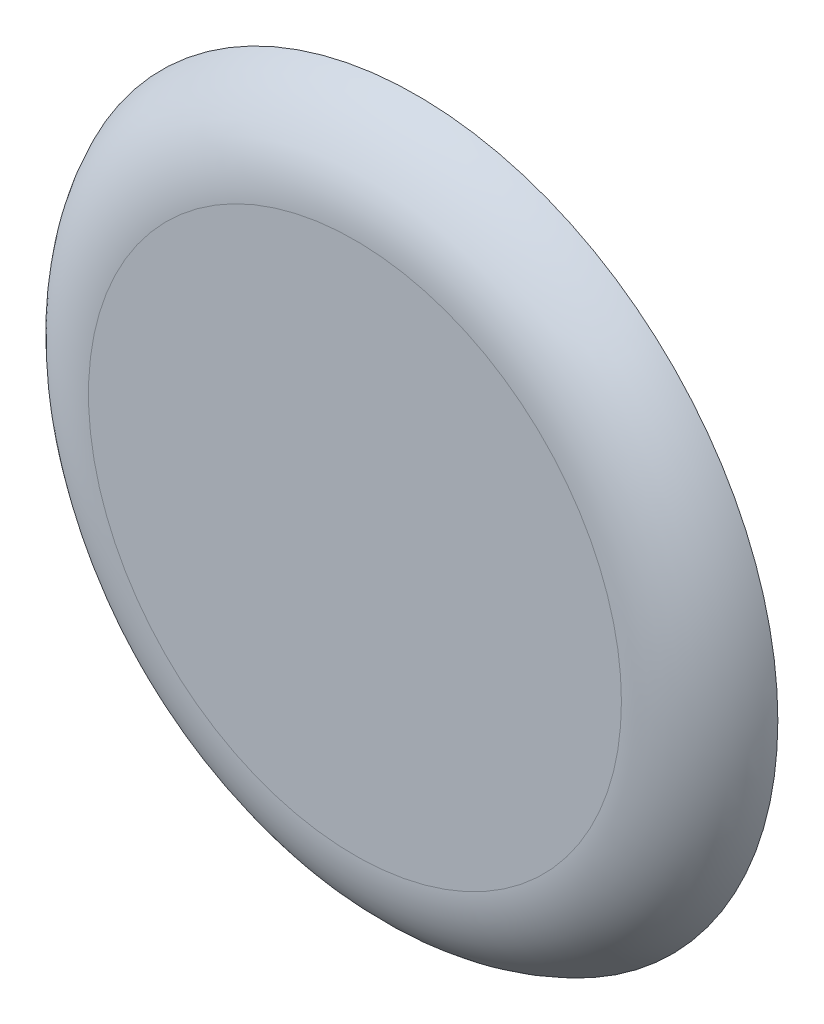
SolidWorks part; units mm, degrees
ref_plane "Přední rovina" through (0, 0, 0) normal (0, 0, 1) x (1, 0, 0)
ref_plane "Horní rovina" through (0, 0, 0) normal (0, 1, 0) x (1, 0, 0)
ref_plane "Pravá rovina" through (0, 0, 0) normal (1, 0, 0) x (0, 0, -1)
sketch "Sketch1" plane through (0, 0, 0) normal (0, 0, 1) x (1, 0, 0)
  circle A0 centre (0, 0) radius 17.5
  dimension "D1" = 35
extrude "Boss-Extrude1" add sketch "Sketch1" along normal blind 3
fillet "Fillet1" radius 5 1 edges at (17.5, 0, 3)
sketch "Sketch3" plane through (0, 0, 0) normal (0, 0, -1) x (1, 0, 0)
  circle A0 centre (0, 0) radius 2.975
  circle A1 centre (0, 5) radius 1.925
  circle A2 centre (0, 10) radius 1.925
  circle A9 centre (5, 0) radius 1.925
  circle A10 centre (10, 0) radius 1.925
  circle A11 centre (0, -5) radius 1.925
  circle A12 centre (0, -10) radius 1.925
  circle A13 centre (-5, 0) radius 1.925
  circle A14 centre (-10, 0) radius 1.925
  point P24 (-1.2398, -2.2452)
  dimension "D1" = 5.95
  dimension "D4" = 3.85
  dimension "D5" = 3.85
  dimension "D2" = 5
  dimension "D3" = 5
  dimension "D6" = 4
extrude "Cut-Extrude1" cut sketch "Sketch3" against normal blind 2
